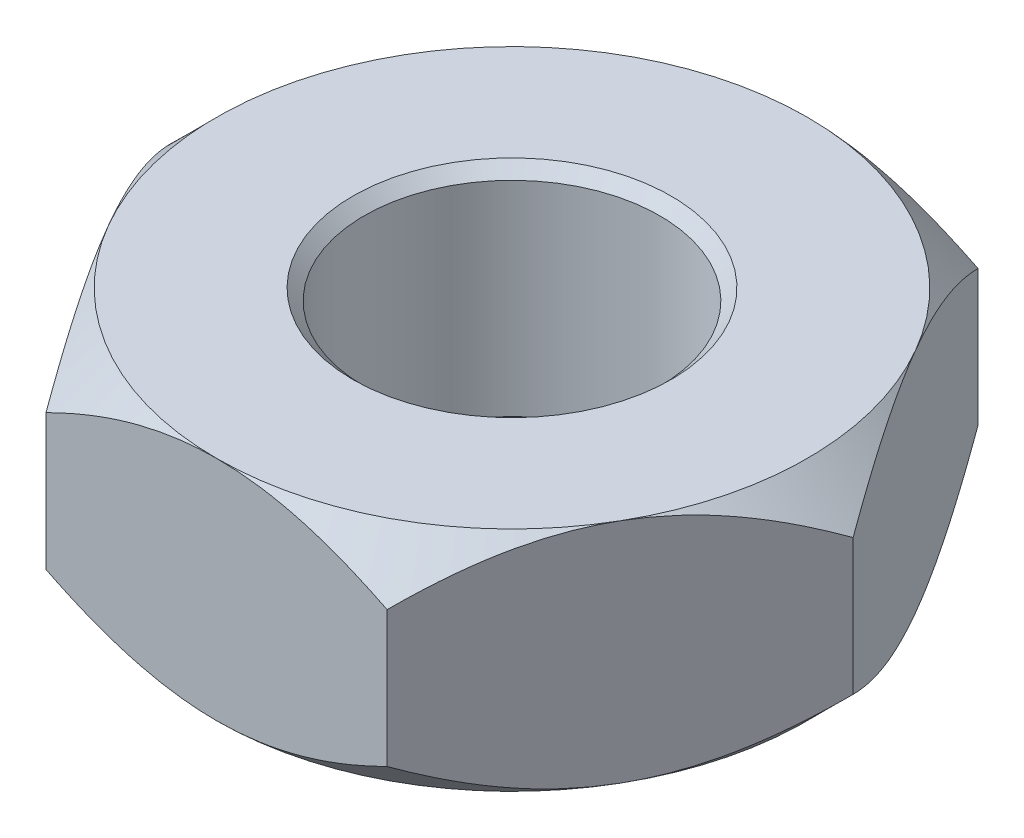
SolidWorks part; units mm, degrees
ref_plane "Front Plane" through (0, 0, 0) normal (0, 0, 1) x (1, 0, 0)
ref_plane "Top Plane" through (0, 0, 0) normal (0, 1, 0) x (1, 0, 0)
ref_plane "Right Plane" through (0, 0, 0) normal (1, 0, 0) x (0, 0, -1)
sketch "Sketch1" plane through (0, 0, 0) normal (0, 1, 0) x (1, 0, 0)
  line L1 (7.5056, 0) -> (3.7528, 6.5)
  line L2 (3.7528, 6.5) -> (-3.7528, 6.5)
  line L3 (-3.7528, 6.5) -> (-7.5056, 0)
  line L4 (-7.5056, 0) -> (-3.7528, -6.5)
  line L5 (-3.7528, -6.5) -> (3.7528, -6.5)
  line L6 (3.7528, -6.5) -> (7.5056, 0)
  circle A0 centre (0, 0) radius 6.5 construction
  circle A1 centre (0, 0) radius 3.25
  dimension "D2" = 6.5
  dimension "D1" = 13
extrude "Boss-Extrude1" add sketch "Sketch1" along normal blind 5 contours L5 L6 L1 L2 L3 L4 A1 region at (5.4572, 0, 3.1507)
sketch "Sketch2" plane through (0, 0, 0) normal (1, 0, 0) x (0, 0, -1)
  line L0 (6.5, 5) -> (7.55, 6.05)
  line L1 (7.55, 6.05) -> (7.55, 3.95)
  line L2 (7.55, 3.95) -> (6.5, 5)
  line L3 (6.5, 2.5) -> (7.8632, 2.5) construction
  line L4 (6.5, 5) -> (6.5, 0) construction
  line L5 (7.55, 1.05) -> (6.5, 0)
  line L6 (7.55, -1.05) -> (7.55, 1.05)
  line L7 (6.5, 0) -> (7.55, -1.05)
  dimension "D1" = 2.1
ref_axis "Axis1" through (0, 5, 0) along (0, -1, 0)
revolve "Cut-Revolve1" cut sketch "Sketch2" angle 360 about axis through (0, 5, 0) along (0, -1, 0)
sketch "Sketch4" plane through (0, 5, 0) normal (0, 1, 0) x (1, 0, 0)
  circle A0 centre (0, 0) radius 4
curve "Helix/Spiral1" [suppressed] pitch 1.25 height 5 turns 4
ref_plane "Plane1" [suppressed] through (0, 5, 4) normal (-0.9988, -0.0497, 0) x (0, 0, 1)
chamfer "Chamfer1" [suppressed] distance 0.5 angle 45
sketch "Sketch5" [suppressed] plane through (0, 5, 4) normal (-0.9988, -0.0497, 0) x (0, 0, 1)
  line L0 (0.4983, 0.146) -> (-0.8007, 0.896)
  line L1 (-0.8007, 0.896) -> (-0.8007, -0.604)
  line L2 (-0.8007, -0.604) -> (0.4983, 0.146)
  line L3 (-0.0006, -0.854) -> (0.1004, -0.854) construction
  dimension "D1" = 1.5
ref_axis "Axis2" through (0, 5, 0) along (0, -1, 0)
chamfer "Chamfer2" distance 0.25 angle 45 2 edges at (0, 5, 3.25) (0, 0, 3.25)
